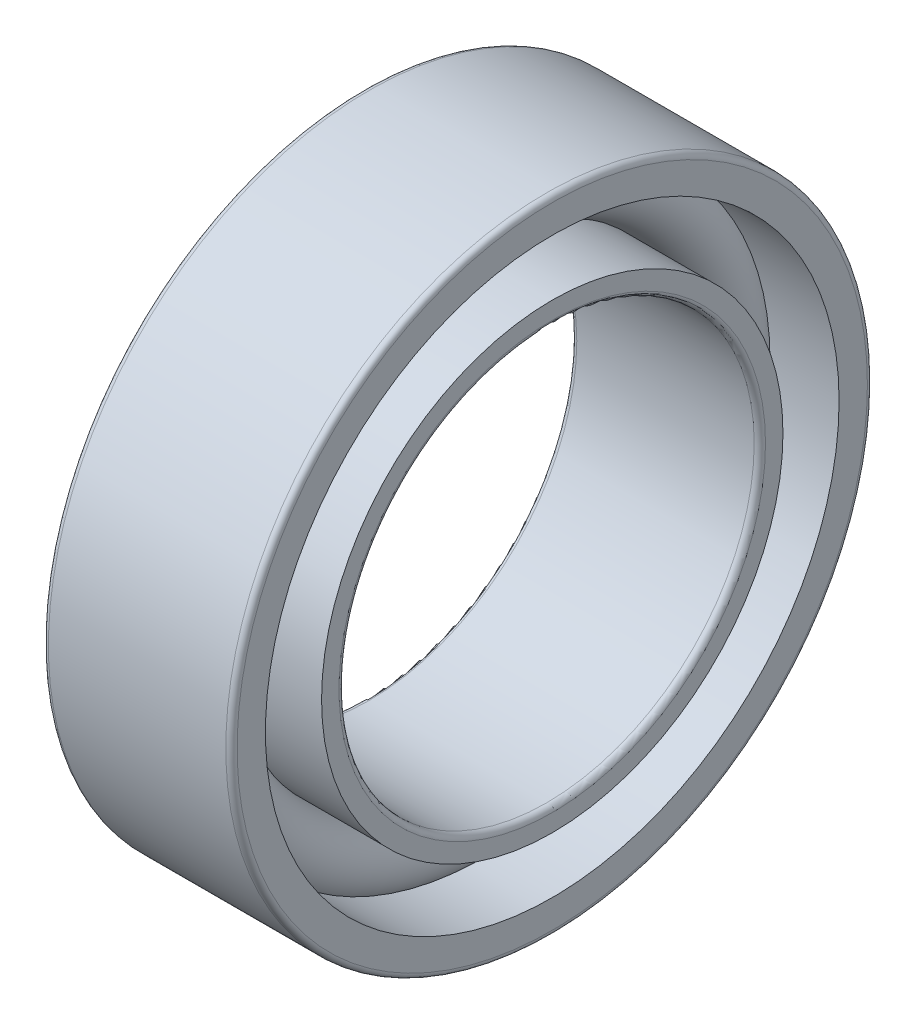
SolidWorks part; units mm, degrees
ref_plane "Plane1" through (0, 0, 0) normal (0, 0, 1) x (1, 0, 0)
ref_plane "Plane2" through (0, 0, 0) normal (0, 1, 0) x (1, 0, 0)
ref_plane "Plane3" through (0, 0, 0) normal (1, 0, 0) x (0, 0, -1)
sketch "Clipboard" plane through (0, 0, 0) normal (0, 0, 1) x (1, 0, 0)
  line L0 (-10, 0) -> (10, 0) construction
  line L1 (0, 0) -> (22.3471, -0.7804)
  line L2 (0, 0) -> (13.9915, 0.4886)
  line L3 (0, 0) -> (22.3471, -0.7804)
  line L4 (0, 0) -> (-22.3573, -0.3902)
  dimension "BallCLRad" = 14
sketch "CagSpiSke" plane through (0, 0, 0) normal (0, 0, 1) x (1, 0, 0)
  line L0 (0.45, 13.7) -> (0.45, 14.3)
  line L1 (0.45, 14.3) -> (-0.45, 14.3)
  line L2 (-0.45, 14.3) -> (-0.45, 13.7)
  line L3 (-0.45, 13.7) -> (0.45, 13.7)
  line L4 (-20.6375, 0) -> (20.6375, 0) construction
  line L5 (0, 0) -> (0, 23.7692) construction
  dimension "OD" = 28.6
  dimension "ID" = 27.4
revolve "CageSpine" add sketch "CagSpiSke" angle 0.001 about L4
ref_axis "Axis1" through (-50, 0, 0) along (1, 0, 0)
sketch "CagBalSke" plane through (0, 0, 0) normal (0, 0, 1) x (1, 0, 0)
  line L0 (-1.98, 14) -> (1.98, 14)
  line L1 (-1.905, 14) -> (1.905, 14) construction
  line L2 (-10, 0) -> (10, 0) construction
  line L3 (0, 0) -> (0, 24) construction
  arc A0 (1.98, 14) -> (-1.98, 14) centre (0, 14) cw
  dimension "BallCLRad" = 14
revolve "CageBall" [suppressed] add sketch "CagBalSke" angle 360 about L1 reverse direction yes
pattern_circular "CageBalls" [suppressed] count 2 every 180 about axis through (-50, 0, 0) along (1, 0, 0)
sketch "CagTrmODSke" plane through (0, 0, 0) normal (0, 0, 1) x (1, 0, 0)
  line L0 (1.981, 14.3) -> (1.981, 15.981)
  line L1 (1.981, 15.981) -> (-1.981, 15.981)
  line L2 (-1.981, 15.981) -> (-1.981, 14.3)
  line L3 (-1.981, 14.3) -> (1.981, 14.3)
  line L4 (-20.6375, 0) -> (20.6375, 0) construction
  line L5 (0, 0) -> (0, 25) construction
  dimension "Width" = 3.962
  dimension "ID" = 28.6
  dimension "OD" = 31.962
revolve "CageTrimOD" [suppressed] cut sketch "CagTrmODSke" angle 360 about L4 reverse direction yes
sketch "CagTrmIDSke" plane through (0, 0, 0) normal (0, 0, 1) x (1, 0, 0)
  line L0 (1.981, 12.021) -> (1.981, 13.7)
  line L1 (1.981, 13.7) -> (-1.981, 13.7)
  line L2 (-1.981, 13.7) -> (-1.981, 12.021)
  line L3 (-1.981, 12.021) -> (1.981, 12.021)
  line L4 (-20.6375, 0) -> (20.6375, 0) construction
  line L5 (0, 0) -> (0, 25) construction
  dimension "Width" = 3.962
  dimension "ID" = 24.042
  dimension "OD" = 27.4
revolve "CageTrimID" [suppressed] cut sketch "CagTrmIDSke" angle 360 about L4 reverse direction yes
sketch "BalSimSke" plane through (0, 0, 0) normal (0, 0, 1) x (1, 0, 0)
  line L0 (-10, 0) -> (10, 0) construction
  line L1 (-10, 14) -> (10, 14) construction
  line L2 (0, 0) -> (0, 23) construction
  circle A0 centre (0, 14) radius 1.8
  dimension "BallCLRad" = 14
  dimension "Ball_diameter" = 3.6
revolve "BallsSimplified" add sketch "BalSimSke" angle 360 about L0
sketch "BalDetSke" plane through (0, 0, 0) normal (0, 0, 1) x (1, 0, 0)
  line L0 (-1.8, 14) -> (1.8, 14)
  line L1 (-1.905, 14) -> (1.905, 14) construction
  line L2 (0, 0) -> (0, 25) construction
  arc A0 (1.8, 14) -> (-1.8, 14) centre (0, 14) cw
  dimension "BallCLRad" = 14
  dimension "Ball_diameter" = 3.6
revolve "BallDetailed" [suppressed] add sketch "BalDetSke" angle 360 about L1 reverse direction yes
sketch "InnRacSke" plane through (0, 0, 0) normal (0, 0, 1) x (1, 0, 0)
  line L0 (-1.3079, 12.8) -> (-5, 12.8)
  line L1 (-5, 12.8) -> (-5, 11.3)
  line L2 (-4.7, 11) -> (4.7, 11)
  line L3 (5, 11.3) -> (5, 12.225)
  line L4 (0, 12.225) -> (5, 12.225)
  line L5 (-20.6375, 0) -> (20.6375, 0) construction
  line L6 (0, 0) -> (0, 30) construction
  arc A0 (-5, 11.3) -> (-4.7, 11) centre (-4.7, 11.3) ccw
  arc A1 (4.7, 11) -> (5, 11.3) centre (4.7, 11.3) ccw
  arc A2 (0, 12.225) -> (-1.3079, 12.8) centre (0, 14) cw
  dimension "BallCLRad" = 14
  dimension "Fillet_radius" = 0.3
  dimension "Ball_diameter" = 3.55
  dimension "ID" = 22
  dimension "OD" = 25.6
  dimension "Width" = 10
revolve "InnerRace" add sketch "InnRacSke" angle 360 about L5 reverse direction yes
sketch "OutRacSke" plane through (0, 0, 0) normal (0, 0, 1) x (1, 0, 0)
  line L0 (0, 15.775) -> (-5, 15.775)
  line L1 (-5, 15.775) -> (-5, 16.7)
  line L2 (-4.7, 17) -> (4.7, 17)
  line L3 (5, 16.7) -> (5, 15.2)
  line L4 (5, 15.2) -> (1.3079, 15.2)
  line L5 (-20.6375, 0) -> (20.6375, 0) construction
  line L6 (0, 0) -> (0, 30) construction
  arc A0 (-5, 16.7) -> (-4.7, 17) centre (-4.7, 16.7) cw
  arc A1 (4.7, 17) -> (5, 16.7) centre (4.7, 16.7) cw
  arc A2 (1.3079, 15.2) -> (0, 15.775) centre (0, 14) ccw
  dimension "BallCLRad" = 14
  dimension "Fillet_radius" = 0.3
  dimension "Ball_diameter" = 3.55
  dimension "Width" = 10
revolve "OuterRace" add sketch "OutRacSke" angle 360 about L5 reverse direction yes
pattern_circular "BallsDetailed" [suppressed] count 2 every 180 about axis through (-50, 0, 0) along (1, 0, 0)
equation "\"BallCLRad@Clipboard\" = ( \"OD@OutRacSke\" + \"ID@InnRacSke\" ) / 4"
equation "\"BallCLRad@BalSimSke\" = \"BallCLRad@Clipboard\""
equation "\"BallCLRad@BalDetSke\" = \"BallCLRad@Clipboard\""
equation "\"BallCLRad@InnRacSke\" = \"BallCLRad@Clipboard\""
equation "\"BallCLRad@OutRacSke\" = \"BallCLRad@Clipboard\""
equation "\"Ball_diameter@InnRacSke\" = \"Ball_diameter@BalDetSke\" - 0.05"
equation "\"Ball_diameter@OutRacSke\" = \"Ball_diameter@BalDetSke\" - 0.05"
equation "\"Ball_diameter@BalSimSke\" = \"Ball_diameter@BalDetSke\""
equation "\"Width@OutRacSke\" = \"Width@InnRacSke\""
equation "\"Fillet_radius@OutRacSke\" = \"Fillet_radius@InnRacSke\""
equation "\"Max_count@Clipboard\" = int( 3.14159265 / atn(( \"Ball_diameter@BalDetSke\" / 2) / sqr( \"BallCLRad@Clipboard\"  *  \"BallCLRad@Clipboard\" - ( \"Ball_diameter@BalDetSke\" / 2) *  ( \"Ball_diameter@BalDetSke\" / 2))))"
equation "\"Max_count@Clipboard\" = ((sgn( \"Max_count@Clipboard\" - \"Count@Clipboard\" )-1)*( \"Max_count@Clipboard\" - \"Count@Clipboard\" ))/-2+ \"Count@Clipboard\""
equation "\"Count@BallsDetailed\" = int( \"Show_count@Clipboard\" ) "
equation "\"Count@BallsDetailed\" = ((sgn( \"Count@BallsDetailed\" - \"Max_count@Clipboard\" )-1)*( \"Count@BallsDetailed\" - \"Max_count@Clipboard\" ))/-2+ \"Max_count@Clipboard\""
equation "\"Count@BallsDetailed\" = ((sgn( \"Count@BallsDetailed\" - \"Min_count@Clipboard\" )+1)*( \"Count@BallsDetailed\" - \"Min_count@Clipboard\"))/2 +\"Min_count@Clipboard\""
equation "\"Angle@BallsDetailed\" = 360.0 / \"Max_count@Clipboard\""
equation "\"BallCLRad@CagBalSke\" = \"BallCLRad@Clipboard\""
equation "\"Count@CageBalls\" = \"Count@BallsDetailed\""
equation "\"Angle@CageBalls\" = \"Angle@BallsDetailed\""
equation "\"Angle@CageSpine\" =  \"Angle@CageBalls\" * ( \"Count@CageBalls\" -1 + int( \"Count@CageBalls\" / \"Max_count@Clipboard\" ) )  + 0.001 -  int( \"Count@CageBalls\" / \"Max_count@Clipboard\" ) * 0.001"
equation "\"Angle@CageSpine\" =  \"Angle@CageSpine\" * int( \"Min_count@Clipboard\" / 2) + int(1 / \"Min_count@Clipboard\")  * 0.001"
equation "\"CageWallOD@CagBalSke\" =  \"Ball_diameter@BalDetSke\" * 1.1"
equation "\"Thickness@CagSpiSke\" =  \"Ball_diameter@BalDetSke\" * 0.25"
equation "\"OD@CagTrmODSke\" = \"BallCLRad@Clipboard\" * 2 + \"CageWallOD@CagBalSke\" + 0.002"
equation "\"ID@CagTrmODSke\" = \"BallCLRad@Clipboard\" * 2 + \"Ball_diameter@BalDetSke\" / 6"
equation "\"OD@CagTrmIDSke\" = \"BallCLRad@Clipboard\" * 2 - \"Ball_diameter@BalDetSke\" / 6"
equation "\"ID@CagTrmIDSke\" = \"BallCLRad@Clipboard\" * 2 - \"CageWallOD@CagBalSke\" + 0.002"
equation "\"OD@CagSpiSke\" = \"ID@CagTrmODSke\""
equation "\"ID@CagSpiSke\" = \"OD@CagTrmIDSke\""
equation "\"Width@CagTrmODSke\" = \"CageWallOD@CagBalSke\" + 0.002"
equation "\"Width@CagTrmIDSke\" = \"CageWallOD@CagBalSke\" + 0.002"
